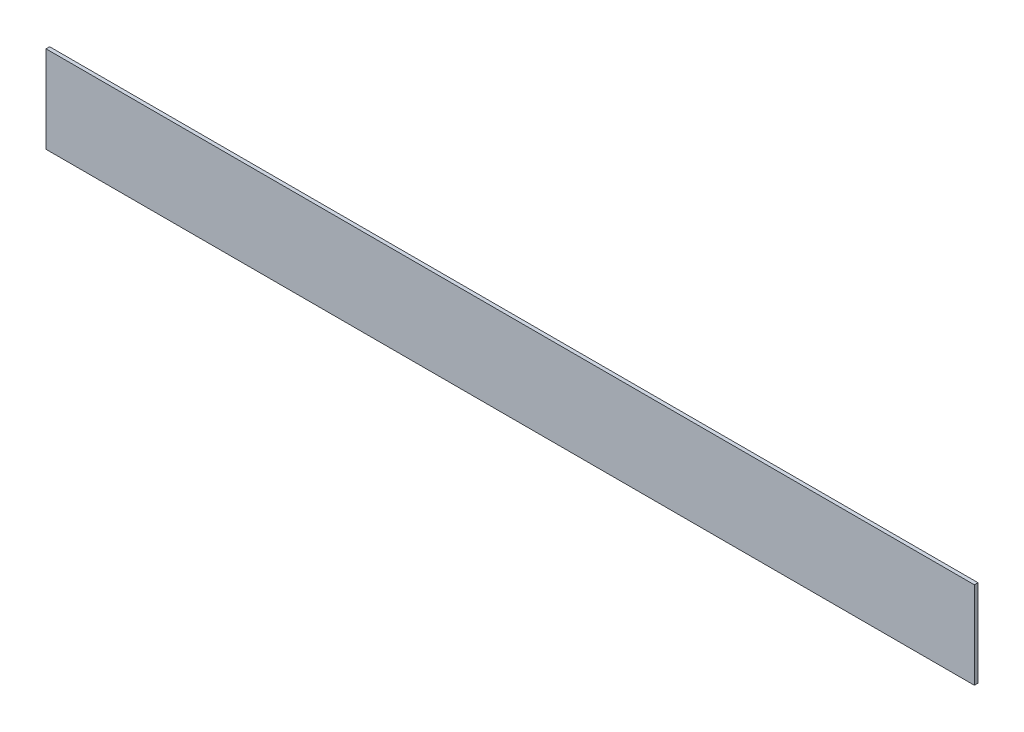
SolidWorks part; units mm, degrees
material "PC High Viscosity"
ref_plane "Front Plane" through (0, 0, 0) normal (0, 0, 1) x (1, 0, 0)
ref_plane "Top Plane" through (0, 0, 0) normal (0, 1, 0) x (1, 0, 0)
ref_plane "Right Plane" through (0, 0, 0) normal (1, 0, 0) x (0, 0, -1)
sketch "Sketch1" plane through (0, 0, 0) normal (0, 1, 0) x (1, 0, 0)
  line L1 (0, 0) -> (406.4, 0)
  line L2 (0, 0) -> (0, 1.5875)
  line L3 (0, 1.5875) -> (406.4, 1.5875)
  line L4 (406.4, 0) -> (406.4, 1.5875)
  dimension "D1" = 406.4
  dimension "D2" = 1.5875
extrude "Boss-Extrude1" add sketch "Sketch1" along normal blind 38.1
